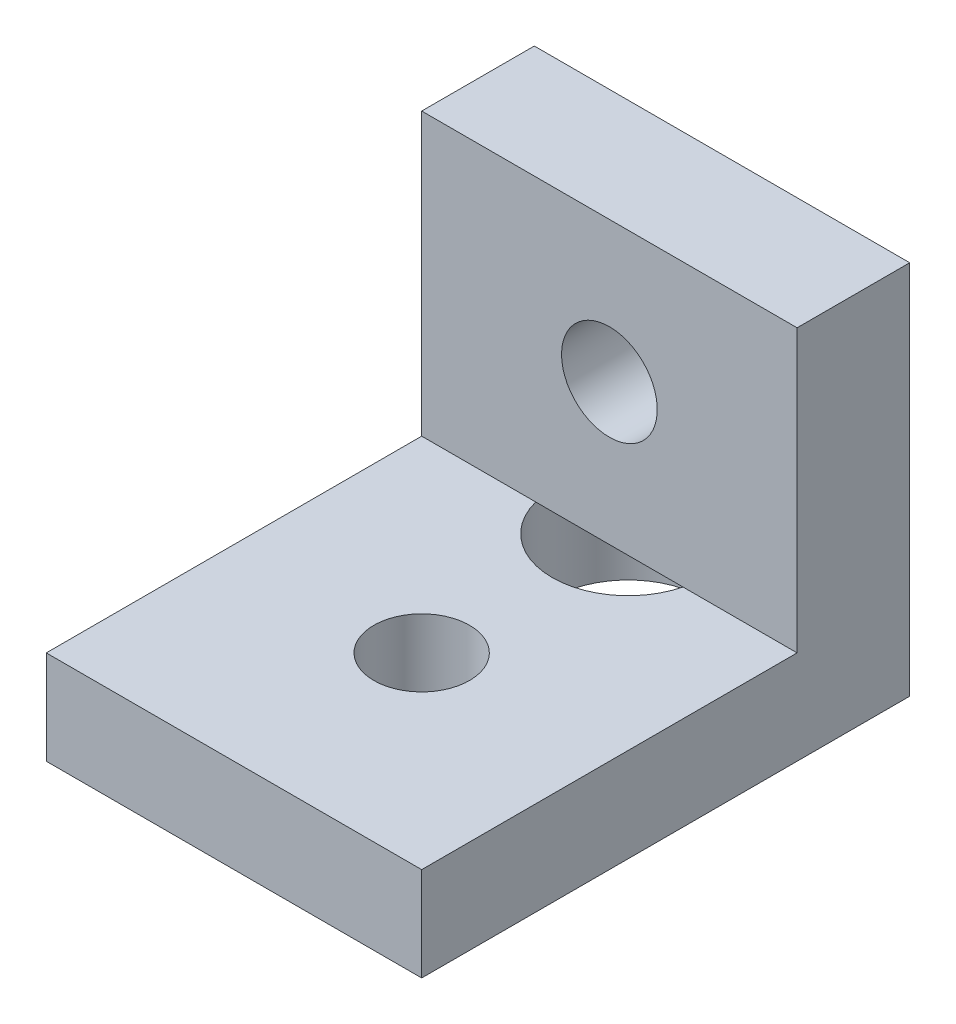
SolidWorks part; units mm, degrees
ref_plane "Front Plane" through (0, 0, 0) normal (0, 0, 1) x (1, 0, 0)
ref_plane "Top Plane" through (0, 0, 0) normal (0, 1, 0) x (1, 0, 0)
ref_plane "Right Plane" through (0, 0, 0) normal (1, 0, 0) x (0, 0, -1)
sketch "Sketch1" plane through (0, 0, 0) normal (0, 1, 0) x (1, 0, 0)
  line L0 (0, 20) -> (20, 20)
  line L1 (0, 0) -> (20, 0)
  line L2 (0, 0) -> (0, 26)
  line L3 (0, 26) -> (20, 26)
  line L4 (20, 0) -> (20, 26)
  line L5 (0, 13) -> (20, 13) construction
  line L6 (0, 7) -> (20, 7) construction
  line L7 (10, 13) -> (10, 7) construction
  line L8 (10, 10) -> (0, 10) construction
  line L9 (10, 20) -> (10, 12.55) construction
  circle A0 centre (10, 10) radius 2.55
  circle A1 centre (10, 21) radius 4.05
  point P20 (10, 19.1898)
  dimension "D6" = 5.1
  dimension "D7" = 8.1
  dimension "D1" = 26
  dimension "D2" = 20
  dimension "D3" = 20
  dimension "D4" = 6
  dimension "D5" = 10
  dimension "D8" = 11
extrude "Boss-Extrude1" add sketch "Sketch1" along normal blind 5 contours A1 L0 L2 L1 L4 A0 | A1 L0 L4 L3 L2 region at (0.2088, 0, -23) region at (3.0377, 0, -19.7172)
extrude "Boss-Extrude2" add sketch "Sketch1<3>" along normal blind 20 contours A1 L0 L4 L3 L2 region at (0.2088, 0, -23)
sketch "Sketch1<3>" plane through (0, 0, 0) normal (0, 1, 0) x (1, 0, 0) same geometry as "Sketch1"
sketch "Sketch3" plane through (0, 5, 0) normal (0, 1, 0) x (1, 0, 0)
  line L0 (20, 0) -> (20, 20) construction
  line L1 (20, 20) -> (13.9246, 20) construction
  line L2 (6.0754, 20) -> (0, 20) construction
  line L3 (0, 20) -> (0, 0) construction
  line L4 (0, 0) -> (20, 0) construction
  line L5 (13.9246, 20) -> (20, 20) construction
  line L6 (20, 20) -> (20, 26) construction
  line L7 (20, 26) -> (0, 26) construction
  line L8 (0, 26) -> (0, 20) construction
  line L9 (0, 20) -> (6.0754, 20) construction
  line L10 (20, 0) -> (20, 20)
  line L11 (20, 20) -> (13.9246, 20)
  line L12 (6.0754, 20) -> (0, 20)
  line L13 (0, 20) -> (0, 0)
  line L14 (0, 0) -> (20, 0)
  line L15 (13.9246, 20) -> (20, 20)
  line L16 (20, 20) -> (20, 26)
  line L17 (20, 26) -> (0, 26)
  line L18 (0, 26) -> (0, 20)
  line L19 (0, 20) -> (6.0754, 20)
  line L20 (13.9246, 20) -> (6.0754, 20)
  arc A0 (6.0754, 20) -> (13.9246, 20) centre (10, 21) ccw construction
  arc A1 (13.9246, 20) -> (6.0754, 20) centre (10, 21) ccw construction
  arc A2 (6.0754, 20) -> (13.9246, 20) centre (10, 21) ccw
  arc A3 (13.9246, 20) -> (6.0754, 20) centre (10, 21) ccw
extrude "Boss-Extrude3" add sketch "Sketch3" along normal up to surface (15 mm away) contours L20 A3 region at (10, 5, -22.1929) up to face at (10, 20, -22.8417)
sketch "Sketch2" plane through (0, 0, -26) normal (0, 0, -1) x (-1, 0, 0)
  line L1 (-20, 5) -> (-20, 20) construction
  line L2 (-20, 20) -> (0, 20) construction
  line L6 (-20, 20) -> (0, 20) construction
  line L7 (0, 20) -> (0, 5) construction
  line L8 (-13.9246, 12.5) -> (-20, 12.5) construction
  line L9 (-20, 5) -> (-20, 20)
  line L10 (-20, 20) -> (0, 20)
  line L11 (-6.0754, 12.5) -> (0, 12.5)
  line L12 (-10, 20) -> (-10, 12.5) construction
  line L14 (-20, 20) -> (0, 20)
  line L15 (0, 20) -> (0, 5)
  line L16 (-6.0754, 12.5) -> (-13.9246, 12.5) construction
  circle A0 centre (-10, 12.5) radius 2.55
  point P13 (0, 0)
  dimension "D1" = 5.1
extrude "Cut-Extrude1" cut sketch "Sketch2" against normal through all contours A0 L16 | L16 A0 region at (10, 12.5, -26)
